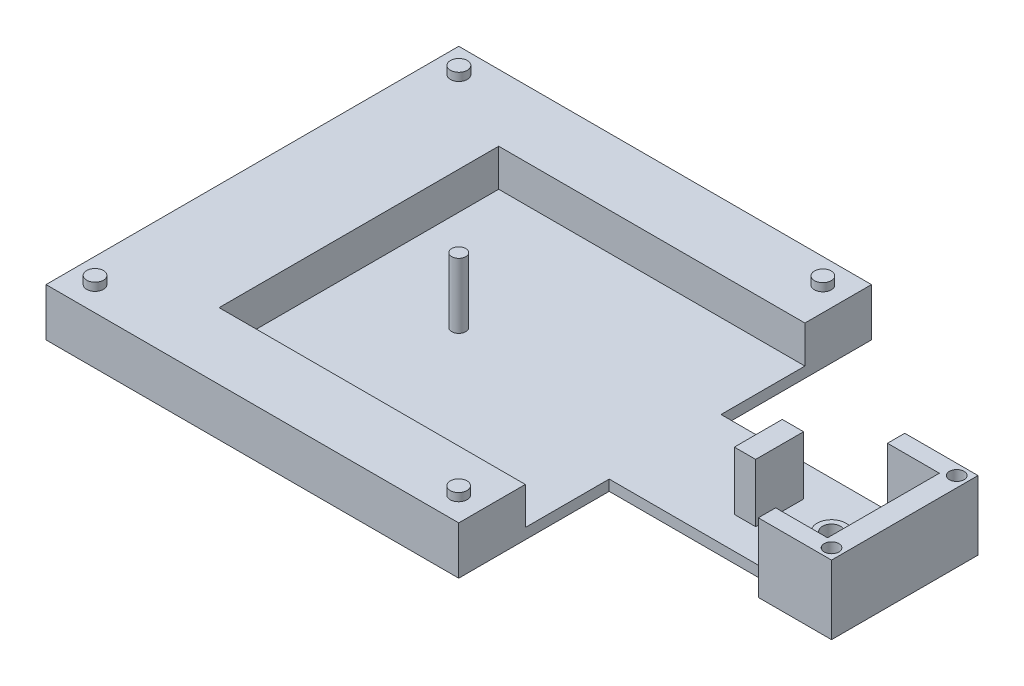
SolidWorks part; units mm, degrees
ref_plane "Front Plane" through (0, 0, 0) normal (0, 0, 1) x (1, 0, 0)
ref_plane "Top Plane" through (0, 0, 0) normal (0, 1, 0) x (1, 0, 0)
ref_plane "Right Plane" through (0, 0, 0) normal (1, 0, 0) x (0, 0, -1)
sketch "Sketch1" plane through (0, 0, 0) normal (0, 1, 0) x (1, 0, 0)
  line L4 (27.5, -27.5) -> (27.5, 27.5)
  line L5 (0, 0) -> (27.5, 27.5) construction
  line L7 (-55, 0) -> (55, 0) construction
  line L9 (19.5, 21) -> (19.5, -21)
  line L18 (0, 21) -> (-62.5, 21)
  line L19 (-217.5, -77.5) -> (-62.5, -77.5)
  line L28 (-217.5, -77.5) -> (-217.5, 77.5)
  line L32 (-217.5, 77.5) -> (-62.5, 77.5)
  line L34 (-217.5, -77.5) -> (-62.5, 77.5) construction
  line L35 (-217.5, 77.5) -> (-62.5, -77.5) construction
  line L36 (0, -21) -> (-62.5, -21)
  line L37 (-62.5, 21) -> (-62.5, 77.5)
  line L38 (-62.5, -21) -> (-62.5, -77.5)
  line L42 (19.5, -21) -> (0, -21)
  line L43 (-19.5, -9) -> (-27.5, -9)
  line L44 (-19.5, -9) -> (-19.5, 9)
  line L45 (-19.5, 9) -> (-27.5, 9)
  line L46 (-27.5, -9) -> (-27.5, 9)
  line L47 (-19.5, -9) -> (-27.5, 9) construction
  line L48 (-19.5, 9) -> (-27.5, -9) construction
  line L49 (0, -55) -> (0, 55) construction
  line L50 (0, -21) -> (0, -27.5)
  line L51 (0, -27.5) -> (27.5, -27.5)
  line L52 (0, 27.5) -> (27.5, 27.5)
  line L53 (19.5, 21) -> (0, 21)
  line L54 (0, 27.5) -> (0, 21)
  circle A1 centre (23.5, 23.5) radius 2.75
  circle A2 centre (23.5, -23.5) radius 2.75
  circle A5 centre (0, 0) radius 3.425
  point P0 (0, 0)
  point P7 (-23.5, 0)
  point P19 (-140, 0)
  dimension "D2" = 155
  dimension "D3" = 55
  dimension "D6" = 155
  dimension "D8" = 6.85
  dimension "D12" = 140
  dimension "D13" = 56.5
  dimension "D14" = 56.5
  dimension "D7" = 5.5
  dimension "D4" = 4
  dimension "D5" = 55
  dimension "D9" = 4
  dimension "D10" = 8
  dimension "D16" = 8
  dimension "D17" = 23.5
  dimension "D15" = 18
extrude "Boss-Extrude1" add sketch "Sketch1" along normal blind 4 contours L9 A5 region at (-125.8481, 0, 0)
extrude "Boss-Extrude2" add sketch "Sketch1<3>" along normal blind 25.9 contours L9 L4 A1 A2 | L46 L43 L44 L45 region at (13.75, 0, 26.8851) region at (-23.5, 0, 0)
sketch "Sketch1<3>" plane through (0, 0, 0) normal (0, 1, 0) x (1, 0, 0) same geometry as "Sketch1"
sketch "Sketch4" plane through (0, 4, 0) normal (0, 1, 0) x (1, 0, 0)
  circle A0 centre (0, 0) radius 3.425
  circle A1 centre (0, 0) radius 5.425
  dimension "D1" = 2
  dimension "D2" = 6.85
extrude "Boss-Extrude5" add sketch "Sketch4" along normal blind 3.7
sketch "Sketch5" plane through (0, 4, 0) normal (0, 1, 0) x (1, 0, 0)
  line L0 (-217.5, 77.5) -> (-62.5, 77.5)
  line L1 (-62.5, 77.5) -> (-62.5, 52.5)
  line L2 (-62.5, 21) -> (-62.5, 77.5) construction
  line L3 (-62.5, 52.5) -> (-177.5, 52.5)
  line L4 (-177.5, 52.5) -> (-177.5, -52.5)
  line L5 (-177.5, -52.5) -> (-62.5, -52.5)
  line L6 (-62.5, -21) -> (-62.5, -77.5) construction
  line L7 (-62.5, -52.5) -> (-62.5, -77.5)
  line L8 (-62.5, -77.5) -> (-217.5, -77.5)
  line L9 (-217.5, -77.5) -> (-217.5, 77.5)
  dimension "D1" = 25
  dimension "D2" = 25
  dimension "D3" = 40
extrude "Boss-Extrude6" add sketch "Sketch5" along normal blind 14
sketch "Sketch6" plane through (0, 18, 0) normal (0, 1, 0) x (1, 0, 0)
  line L0 (-62.5, 77.5) -> (-217.5, 77.5) construction
  line L1 (-62.5, 52.5) -> (-62.5, 77.5) construction
  line L2 (-62.5, -77.5) -> (-62.5, -52.5) construction
  line L3 (-217.5, -77.5) -> (-62.5, -77.5) construction
  line L4 (-217.5, 77.5) -> (-217.5, -77.5) construction
  circle A0 centre (-71.48, 68.23) radius 3.15
  circle A1 centre (-71.61, -68.43) radius 3.15
  circle A2 centre (-208.29, -68.29) radius 3.15
  circle A3 centre (-208.265, 68.315) radius 3.175
  dimension "D3" = 6.3
  dimension "D6" = 6.3
  dimension "D11" = 6.35
  dimension "D12" = 6.3
  dimension "D1" = 9.27
  dimension "D2" = 8.98
  dimension "D4" = 9.11
  dimension "D5" = 9.07
  dimension "D7" = 9.21
  dimension "D8" = 9.21
  dimension "D9" = 9.235
  dimension "D10" = 9.185
extrude "Boss-Extrude7" add sketch "Sketch6" along normal blind 3
sketch "Sketch7" plane through (0, 4, 0) normal (0, 1, 0) x (1, 0, 0)
  line L0 (-217.5, 77.5) -> (-62.5, -77.5) construction
  line L1 (-217.5, -77.5) -> (-62.5, 77.5) construction
  circle A0 centre (-140, 0) radius 2.65
  dimension "D1" = 5.3
extrude "Boss-Extrude8" add sketch "Sketch7" along normal blind 24.4
